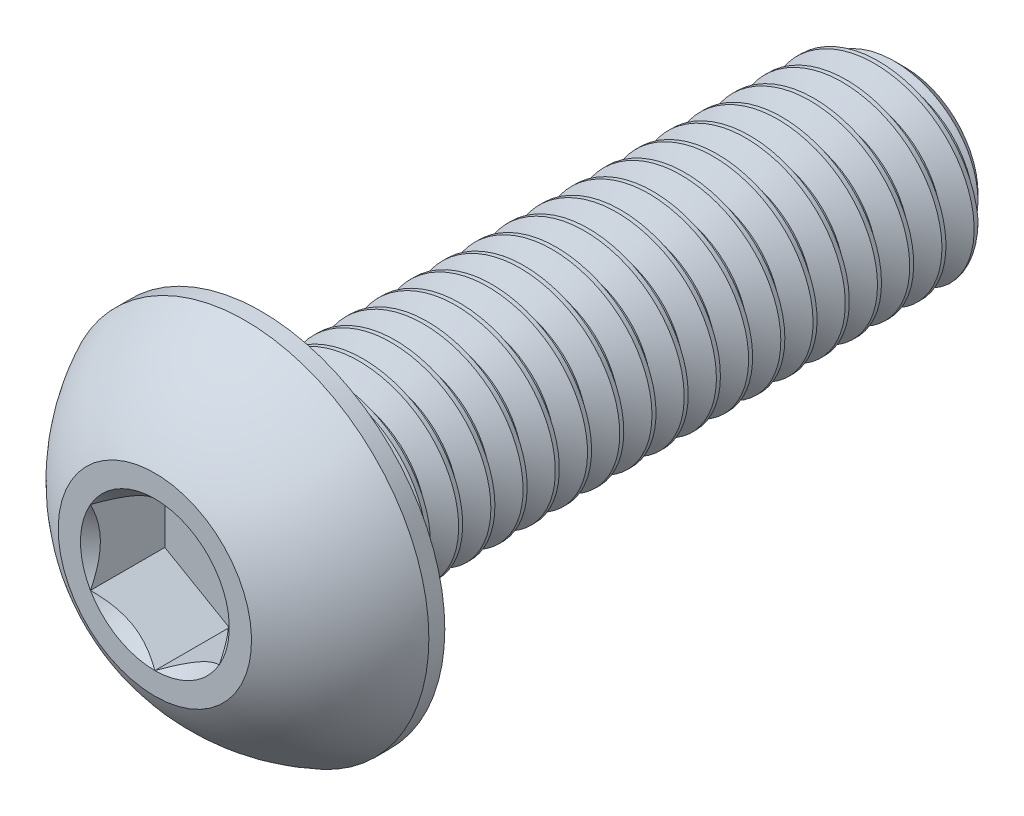
SolidWorks part; units mm, degrees
ref_plane "Front" through (0, 0, 0) normal (0, 0, 1) x (1, 0, 0)
ref_plane "Top" through (0, 0, 0) normal (0, 1, 0) x (1, 0, 0)
ref_plane "Right" through (0, 0, 0) normal (1, 0, 0) x (0, 0, -1)
sketch "Sketch1" plane through (0, 0, 0) normal (1, 0, 0) x (0, 0, -1)
  line L2 (1.65, 1.5) -> (11.65, 1.5)
  line L3 (11.65, 1.5) -> (11.65, 0)
  line L4 (11.65, 0) -> (1.65, 0)
  line L6 (1.4025, 2.85) -> (1.65, 2.85) construction
  line L7 (11.65, 1.5) -> (11.65, -1.5) construction
  line L8 (0, 0) -> (1.65, 0) construction
  line L9 (1.65, 2.85) -> (1.65, -2.85) construction
  line L11 (1.65, 1.5) -> (1.65, 0)
  line L13 (0, 1) -> (0, -1) construction
  line L14 (0, 1) -> (0, 1.5) construction
  line L15 (11.65, -1.5) -> (11.15, -1.5) construction
  arc A3 (0, 1.5) -> (1.4025, 2.85) centre (2.7948, 0) cw construction
  dimension "D1" = 0.2475
  dimension "Pitch" = 0.5
revolve "Revolve1" add sketch "Sketch1" angle 360 mid plane about L4
sketch "Sketch7" plane through (0, 0, 0) normal (1, 0, 0) x (0, 0, -1)
  line L6 (1.4025, 2.85) -> (1.65, 2.85) construction
  line L8 (0, 0) -> (1.65, 0) construction
  line L11 (1.65, 2.85) -> (1.65, -2.85) construction
  line L12 (1.4025, 2.85) -> (1.65, 2.85)
  line L13 (0, 0) -> (1.65, 0)
  line L14 (0, 1) -> (0, -1) construction
  line L15 (1.65, 2.85) -> (1.65, 0)
  line L16 (0, 1.5) -> (0, 0)
  arc A2 (1.4025, 2.85) -> (0, 1.5) centre (2.7948, 0) ccw construction
  arc A3 (1.4025, 2.85) -> (0, 1.5) centre (2.7948, 0) ccw
revolve "Revolve2" add sketch "Sketch7" angle 360 mid plane about L13
sketch "Sketch5" plane through (0, 0, 0) normal (0, 0, 1) x (1, 0, 0)
  line L1 (1, -0.5774) -> (1, 0.5774)
  line L2 (1, 0.5774) -> (0, 1.1547)
  line L3 (0, 1.1547) -> (-1, 0.5774)
  line L4 (-1, 0.5774) -> (-1, -0.5774)
  line L5 (-1, -0.5774) -> (0, -1.1547)
  line L6 (0, -1.1547) -> (1, -0.5774)
  circle A0 centre (0, 0) radius 1 construction
extrude "Cut-Extrude2" cut sketch "Sketch5" against normal blind 1.155
sketch "Sketch6" plane through (0, 0, 0) normal (0, 0, 1) x (1, 0, 0)
  circle A0 centre (0, 0) radius 1.1547
extrude "Cut-Extrude3" cut sketch "Sketch6" against normal blind 1.155 draft 45
sketch "Sketch11" plane through (0, 0, 0) normal (1, 0, 0) x (0, 0, -1)
  line L0 (1.65, -2.85) -> (1.65, 2.85)
  point P4 (1.65, 0)
split "Split1" trim tools "Sketch11" bodies to split 113 resulting bodies 119 120
sketch "Sketch10" plane through (0, 0, 0) normal (1, 0, 0) x (0, 0, -1)
  line L0 (11.65, 1.5) -> (11.65, -1.5) construction
  point P0 (10.9, -1.5)
  dimension "D1" = 0.75
sketch "Sketch3" plane through (0, 0, -11.65) normal (0, 0, -1) x (-1, 0, 0)
  circle A0 centre (0, 0) radius 1.5
curve "Helix/Spiral1" pitch 0.5 height 10.5 radius 1.5 centre (0, 0, -11.65) axis (0, 0, 1) start towards (0, 1, 0)
sketch "Sketch2" plane through (0, 0, 0) normal (1, 0, 0) x (0, 0, -1)
  line L0 (11.6188, 1.5541) -> (12.1188, 1.5541) construction
  line L1 (12.1188, 1.5541) -> (11.8688, 1.1211) construction
  line L2 (11.8688, 1.1211) -> (11.6188, 1.5541) construction
  line L3 (11.8688, 1.5541) -> (11.8688, 1.5) construction
  line L4 (11.8688, 1.5) -> (11.8688, 1.1752) construction
  line L5 (11.8688, 1.1752) -> (11.8688, 1.1211) construction
  line L6 (11.8375, 1.1752) -> (11.9, 1.1752)
  line L7 (11.65, 1.5) -> (12.0875, 1.5) construction
  line L8 (11.6344, 1.5271) -> (12.1031, 1.5271)
  line L9 (11.6344, 1.5271) -> (11.8375, 1.1752)
  line L10 (12.1031, 1.5271) -> (11.9, 1.1752)
  point P10 (11.8688, 1.1752)
  point P13 (11.8688, 1.5)
  point P16 (11.8688, 1.5271)
  dimension "D1" = 0.5
  dimension "D2" = 0.0625
chamfer "Chamfer1" distance 0.375 angle 45 1 edges at (0, 1.5, -11.65)
sweep "Cut-Sweep1" cut profiles "Sketch2" path "Helix/Spiral1" align with end faces yes
combine bodies "Combine1" operation type add bodies to combine 120 114
equation "\"D3@Helix/Spiral1\" = \"Lg@Sketch1\" + \"D4@Helix/Spiral1\""
equation "\"D1@Chamfer1\" = \"D4@Helix/Spiral1\" * .75"
equation "\"D1@Cut-Extrude2\" = \"Head Ht@Sketch1\" * .7"
equation "\"D1@Sketch1\" = \"Head Ht@Sketch1\" * .15"
equation "\"D1@Sketch10\" = \"D4@Helix/Spiral1\" * 1.5"
equation "\"D1@Cut-Extrude3\" = \"D1@Cut-Extrude2\""
equation "\"D4@Helix/Spiral1\"=\"Pitch@Sketch1\""
equation "\"D1@Sketch2\"=\"Pitch@Sketch1\""
equation "\"D2@Sketch2\"=\"D1@Sketch2\"/8"
